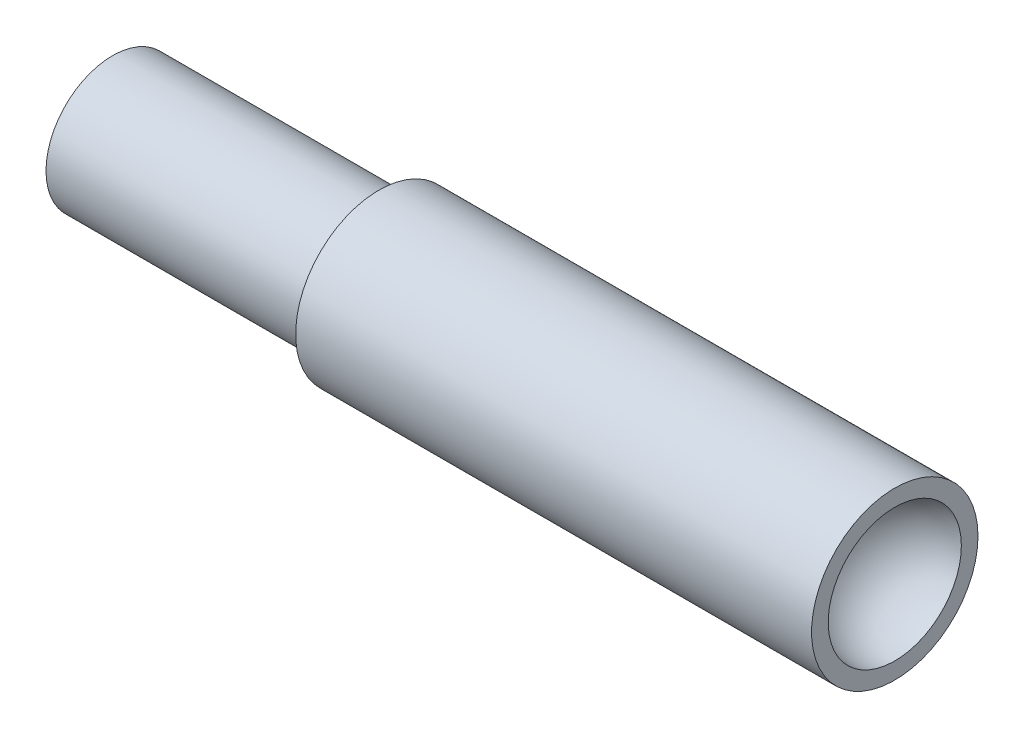
SolidWorks part; units mm, degrees
ref_plane "Front Plane" through (0, 0, 0) normal (0, 0, 1) x (1, 0, 0)
ref_plane "Top Plane" through (0, 0, 0) normal (0, 1, 0) x (1, 0, 0)
ref_plane "Right Plane" through (0, 0, 0) normal (1, 0, 0) x (0, 0, -1)
sketch "Sketch1" plane through (0, 0, 0) normal (1, 0, 0) x (0, 0, -1)
  circle A0 centre (0, 0) radius 25
  dimension "D1" = 50
extrude "Boss-Extrude1" add sketch "Sketch1" along normal blind 155
ref_plane "Plane1" through (156.016, 0, 0) normal (1, 0, 0) x (0, 0, -1)
sketch "Sketch2" plane through (155, 0, 0) normal (1, 0, 0) x (0, 0, -1)
  line L0 (-20, 0) -> (20, 0)
  arc A2 (-20, 0) -> (20, 0) centre (0, 0) cw
  dimension "D1" = 20
revolve "Cut-Revolve3" cut sketch "Sketch2" angle 360 about L0 reverse direction yes
sketch "Sketch3" plane through (0, 0, 0) normal (-1, 0, 0) x (0, 0, 1)
  circle A0 centre (0, 0) radius 20
  dimension "D1" = 40
extrude "Cut-Extrude1" cut sketch "Sketch3" against normal blind 100
ref_plane "Plane2" through (160, 0, 0) normal (1, 0, 0) x (0, 0, -1)
sketch "Sketch4" plane through (160, 0, 0) normal (1, 0, 0) x (0, 0, -1)
  circle A0 centre (0, 0) radius 25 construction
  circle A1 centre (0, 0) radius 25
extrude "Boss-Extrude2" add sketch "Sketch3<2>" along normal blind 80 separate body
sketch "Sketch3<2>" plane through (0, 0, 0) normal (-1, 0, 0) x (0, 0, 1) same geometry as "Sketch3"
